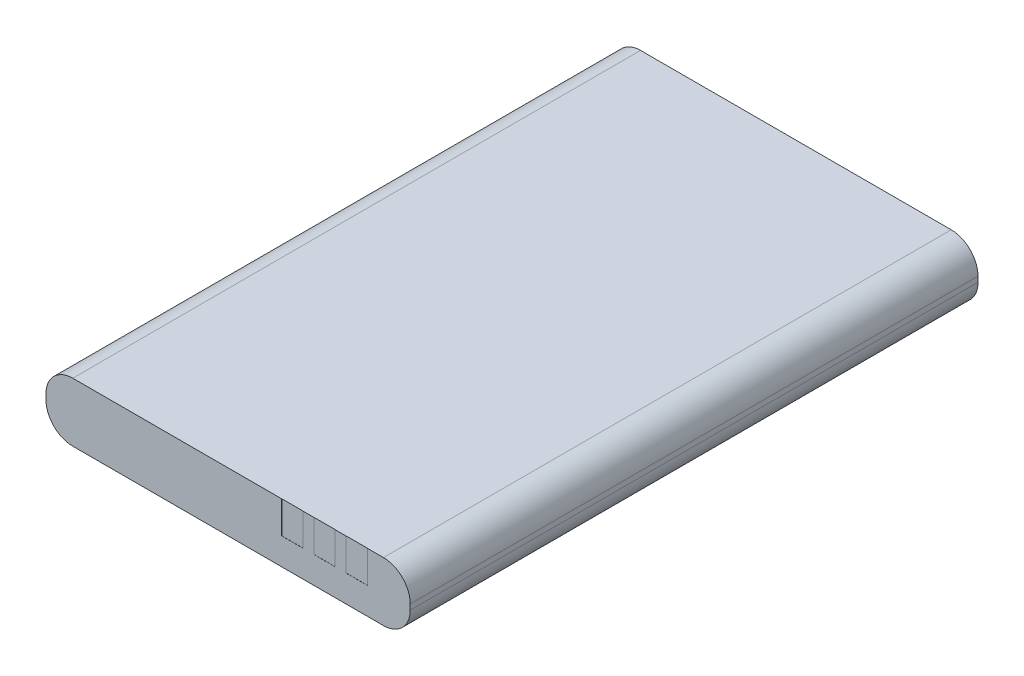
SolidWorks part; units mm, degrees
ref_plane "Front Plane" through (0, 0, 0) normal (0, 0, 1) x (1, 0, 0)
ref_plane "Top Plane" through (0, 0, 0) normal (0, 1, 0) x (1, 0, 0)
ref_plane "Right Plane" through (0, 0, 0) normal (1, 0, 0) x (0, 0, -1)
ref_axis "X-Axis" through (-88.99, 0, 0) along (1, 0, 0)
ref_axis "Y-Axis" through (0, 55, 0) along (0, -1, 0)
ref_axis "Z-Axis" through (0, 0, -88.99) along (0, 0, 1)
sketch "Sketch1" plane through (0, 0, 0) normal (0, 1, 0) x (1, 0, 0)
  line L1 (-17, -26.5) -> (17, -26.5)
  line L2 (-17, -26.5) -> (-17, 26.5)
  line L3 (-17, 26.5) -> (17, 26.5)
  line L4 (17, -26.5) -> (17, 26.5)
  line L5 (-17, -26.5) -> (17, 26.5) construction
  line L6 (-17, 26.5) -> (17, -26.5) construction
  point P0 (0, 0)
  dimension "D1" = 53
  dimension "D2" = 34
extrude "Boss-Extrude1" add sketch "Sketch1" along normal blind 5.5
fillet "Fillet1" radius 2.5 4 edges at (-17, 0, 0) (-17, 5.5, 0) (17, 0, 0) (17, 5.5, 0)
sketch "Sketch2" plane through (0, 0, 26.5) normal (0, 0, 1) x (1, 0, 0)
  line L1 (7, 2.5) -> (5, 2.5)
  line L2 (7, 2.5) -> (7, 5.5)
  line L3 (7, 5.5) -> (5, 5.5)
  line L4 (5, 2.5) -> (5, 5.5)
  line L5 (-14.5, 5.5) -> (14.5, 5.5) construction
  point P4 (0, 0)
  dimension "D1" = 5
  dimension "D2" = 2
  dimension "D3" = 3
extrude "Cut-Extrude1" cut sketch "Sketch2" against normal blind 0.01
pattern_linear "LPattern1" count 3 spacing 3 along (1, 0, 0) of "Cut-Extrude1"
